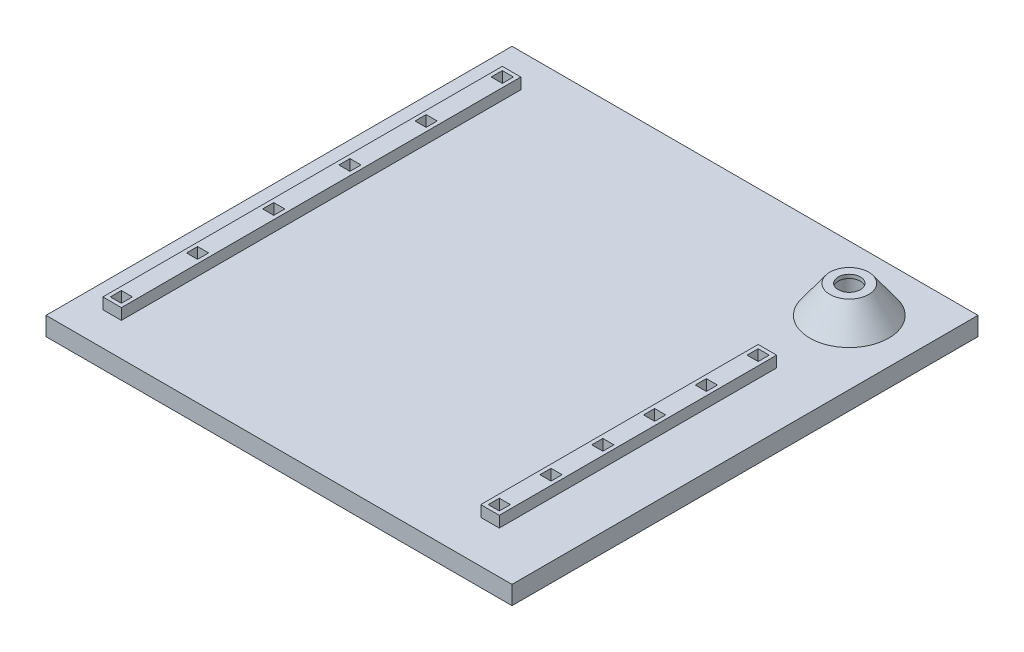
SolidWorks part; units mm, degrees
ref_plane "Front Plane" through (0, 0, 0) normal (0, 0, 1) x (1, 0, 0)
ref_plane "Top Plane" through (0, 0, 0) normal (0, 1, 0) x (1, 0, 0)
ref_plane "Right Plane" through (0, 0, 0) normal (1, 0, 0) x (0, 0, -1)
sketch "Sketch1" plane through (0, 0, 0) normal (0, 1, 0) x (1, 0, 0)
  line L1 (0, 0) -> (126, 0)
  line L2 (0, 0) -> (0, 126)
  line L3 (0, 126) -> (126, 126)
  line L4 (126, 0) -> (126, 126)
  dimension "D1" = 126
  dimension "D2" = 126
extrude "Boss-Extrude1" add sketch "Sketch1" along normal blind 5
sketch "Sketch3" plane through (0, 5, 0) normal (0, 1, 0) x (1, 0, 0)
  line L0 (108.6, 121.1) -> (108.6, 96.1) construction
  circle A0 centre (108.6, 108.6) radius 12.5
extrude "Boss-Extrude2" add sketch "Sketch3" along normal blind 7.5
sketch "Sketch4" plane through (0, 0, 0) normal (0, -1, 0) x (1, 0, 0)
  circle A1 centre (108.6, -108.6) radius 3.45
  dimension "D1" = 6.9
extrude "Cut-Extrude1" cut sketch "Sketch4" against normal blind 11.5
sketch "Sketch6" plane through (0, 12.5, 0) normal (0, 1, 0) x (1, 0, 0)
  line L0 (108.6, 121.1) -> (108.6, 96.1) construction
  circle A0 centre (108.6, 108.6) radius 12.5 construction
  circle A1 centre (108.6, 108.6) radius 3
  dimension "D1" = 6
extrude "Cut-Extrude2" cut sketch "Sketch6" against normal through all
chamfer "Chamfer1" distance 10 angle 36 1 edges at (108.6, 12.5, -96.1) first distance on face at (108.6, 12.5, -96.1)
sketch "Sketch9" plane through (0, 5, 0) normal (0, 1, 0) x (1, 0, 0)
  line L1 (111.1, 11.4582) -> (106.1, 11.4582)
  line L2 (0, 0) -> (126, 0) construction
  line L3 (111.1, 11.4582) -> (111.1, 86.4582)
  line L4 (108.6, 97.9164) -> (108.6, 0)
  line L5 (111.1, 86.4582) -> (106.1, 86.4582)
  line L6 (106.1, 11.4582) -> (106.1, 86.4582)
  line L7 (111.1, 11.4582) -> (106.1, 86.4582) construction
  line L8 (111.1, 86.4582) -> (106.1, 11.4582) construction
  circle A0 centre (108.6, 108.6) radius 10.6836 construction
  point P0 (108.6, 48.9582)
  point P5 (115.3692, 53.7951)
  dimension "D1" = 75
  dimension "D2" = 5
extrude "Boss-Extrude4" add sketch "Sketch9" along normal blind 3 contours L3 L5 L6 L1
sketch "Sketch10" plane through (0, 8, 0) normal (0, 1, 0) x (1, 0, 0)
  line L0 (108.6, 86.4582) -> (108.6, 11.4582) construction
  line L1 (111.1, 86.4582) -> (106.1, 86.4582) construction
  line L2 (111.1, 11.4582) -> (106.1, 11.4582) construction
  line L9 (110.1, 82.4582) -> (107.1, 82.4582)
  line L10 (110.1, 82.4582) -> (110.1, 85.4582)
  line L11 (110.1, 85.4582) -> (107.1, 85.4582)
  line L12 (107.1, 82.4582) -> (107.1, 85.4582)
  line L13 (110.1, 82.4582) -> (107.1, 85.4582) construction
  line L14 (110.1, 85.4582) -> (107.1, 82.4582) construction
  line L18 (110.1, 68.4589) -> (110.1, 71.4589)
  line L19 (110.1, 71.4589) -> (107.1, 71.4589)
  line L20 (107.1, 68.4589) -> (107.1, 71.4589)
  line L21 (110.1, 68.4589) -> (107.1, 68.4589)
  line L22 (110.1, 54.4597) -> (110.1, 57.4597)
  line L23 (110.1, 57.4597) -> (107.1, 57.4597)
  line L24 (107.1, 54.4597) -> (107.1, 57.4597)
  line L25 (110.1, 54.4597) -> (107.1, 54.4597)
  line L26 (110.1, 40.4604) -> (110.1, 43.4604)
  line L27 (110.1, 43.4604) -> (107.1, 43.4604)
  line L28 (107.1, 40.4604) -> (107.1, 43.4604)
  line L29 (110.1, 40.4604) -> (107.1, 40.4604)
  line L30 (110.1, 26.4612) -> (110.1, 29.4612)
  line L31 (110.1, 29.4612) -> (107.1, 29.4612)
  line L32 (107.1, 26.4612) -> (107.1, 29.4612)
  line L33 (110.1, 26.4612) -> (107.1, 26.4612)
  line L34 (110.1, 12.4619) -> (110.1, 15.4619)
  line L35 (110.1, 15.4619) -> (107.1, 15.4619)
  line L36 (107.1, 12.4619) -> (107.1, 15.4619)
  line L37 (110.1, 12.4619) -> (107.1, 12.4619)
  point P13 (108.6, 83.9582)
  dimension "D2" = 3
  dimension "D3" = 3
  dimension "D4" = 6
extrude "Cut-Extrude4" cut sketch "Sketch10" against normal through all
sketch "Sketch11" plane through (0, 5, 0) normal (0, 1, 0) x (1, 0, 0)
  line L5 (8.8811, 126) -> (8.8811, 0) construction
  line L7 (11.3811, 9) -> (6.3811, 9)
  line L8 (11.3811, 9) -> (11.3811, 117)
  line L9 (11.3811, 117) -> (6.3811, 117)
  line L10 (6.3811, 9) -> (6.3811, 117)
  line L11 (11.3811, 9) -> (6.3811, 117) construction
  line L12 (11.3811, 117) -> (6.3811, 9) construction
  point P9 (8.8811, 63)
  dimension "D1" = 108
  dimension "D2" = 5
extrude "Boss-Extrude5" add sketch "Sketch11" along normal blind 3
sketch "Sketch12" plane through (0, 8, 0) normal (0, 1, 0) x (1, 0, 0)
  line L5 (8.8811, 117) -> (8.8811, 112) construction
  line L7 (10.3811, 113) -> (7.3811, 113)
  line L8 (10.3811, 113) -> (10.3811, 116)
  line L9 (10.3811, 116) -> (7.3811, 116)
  line L10 (7.3811, 113) -> (7.3811, 116)
  line L11 (10.3811, 113) -> (7.3811, 116) construction
  line L12 (10.3811, 116) -> (7.3811, 113) construction
  line L17 (10.3811, 95.4002) -> (7.3811, 95.4002)
  line L18 (7.3811, 92.4002) -> (7.3811, 95.4002)
  line L19 (10.3811, 92.4002) -> (7.3811, 92.4002)
  line L20 (10.3811, 92.4002) -> (10.3811, 95.4002)
  line L21 (10.3811, 74.8003) -> (7.3811, 74.8003)
  line L22 (7.3811, 71.8003) -> (7.3811, 74.8003)
  line L23 (10.3811, 71.8003) -> (7.3811, 71.8003)
  line L24 (10.3811, 71.8003) -> (10.3811, 74.8003)
  line L25 (10.3811, 54.2005) -> (7.3811, 54.2005)
  line L26 (7.3811, 51.2005) -> (7.3811, 54.2005)
  line L27 (10.3811, 51.2005) -> (7.3811, 51.2005)
  line L28 (10.3811, 51.2005) -> (10.3811, 54.2005)
  line L29 (10.3811, 33.6007) -> (7.3811, 33.6007)
  line L30 (7.3811, 30.6007) -> (7.3811, 33.6007)
  line L31 (10.3811, 30.6007) -> (7.3811, 30.6007)
  line L32 (10.3811, 30.6007) -> (10.3811, 33.6007)
  line L33 (10.3811, 13.0008) -> (7.3811, 13.0008)
  line L34 (7.3811, 10.0008) -> (7.3811, 13.0008)
  line L35 (10.3811, 10.0008) -> (7.3811, 10.0008)
  line L36 (10.3811, 10.0008) -> (10.3811, 13.0008)
  point P9 (8.8811, 114.5)
  dimension "D2" = 3
  dimension "D3" = 3
  dimension "D4" = 6
extrude "Cut-Extrude5" cut sketch "Sketch12" against normal through all
